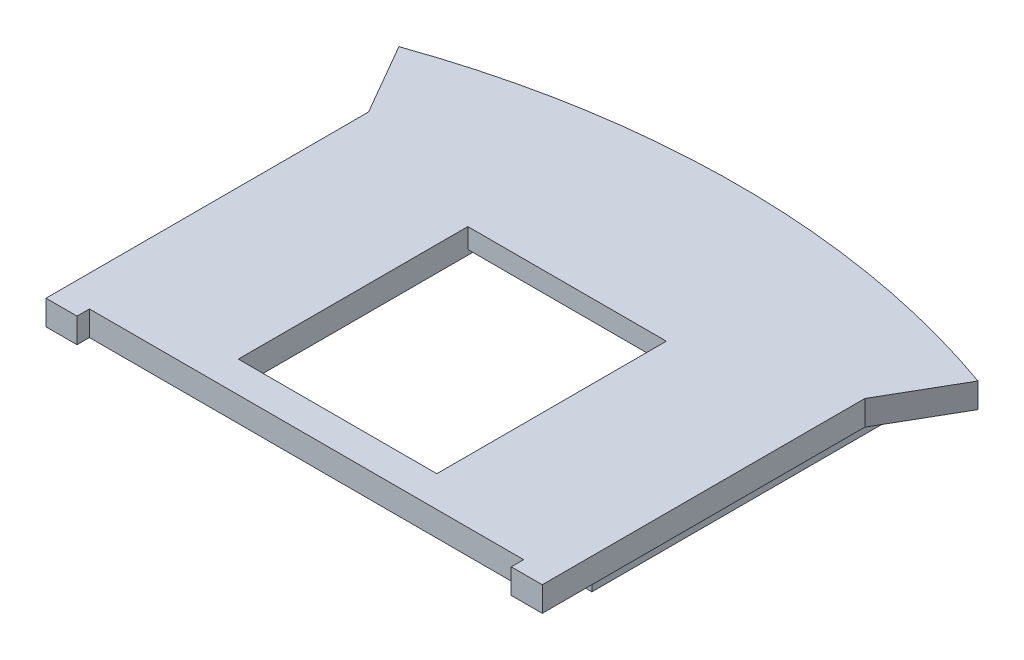
SolidWorks part; units mm, degrees
ref_plane "Front Plane" through (0, 0, 0) normal (0, 0, 1) x (1, 0, 0)
ref_plane "Top Plane" through (0, 0, 0) normal (0, 1, 0) x (1, 0, 0)
ref_plane "Right Plane" through (0, 0, 0) normal (1, 0, 0) x (0, 0, -1)
sketch "Sketch1" plane through (0, 0, 0) normal (0, 1, 0) x (1, 0, 0)
  line L0 (-40, 68) -> (-40, 120)
  line L1 (-40, 120) -> (-46.6772, 131.5652)
  line L2 (46.6772, 131.5652) -> (40, 120)
  line L3 (40, 120) -> (40, 68)
  line L4 (40, 68) -> (-40, 68)
  arc A0 (-46.6772, 131.5652) -> (46.6772, 131.5652) centre (0, 0) cw
  dimension "D1" = 139.6
  dimension "D2" = 150
  dimension "D3" = 40
  dimension "D4" = 80
  dimension "D5" = 150
  dimension "D6" = 52
  dimension "D7" = 68
extrude "Boss-Extrude1" add sketch "Sketch1" along normal blind 4
sketch "Sketch2" plane through (0, 4, 0) normal (0, 1, 0) x (1, 0, 0)
  line L1 (-16, 112) -> (16, 112)
  line L2 (-16, 112) -> (-16, 75)
  line L3 (-16, 75) -> (16, 75)
  line L4 (16, 112) -> (16, 75)
  dimension "D1" = 32
  dimension "D2" = 37
  dimension "D3" = 75
  dimension "D4" = 16
extrude "Cut-Extrude1" cut sketch "Sketch2" against normal up to next
sketch "Sketch3" plane through (0, 0, 0) normal (0, -1, 0) x (1, 0, 0)
  line L0 (16, -75) -> (16, -112) construction
  line L1 (-16, -71.5) -> (16, -71.5)
  line L2 (-16, -71.5) -> (-16, -115.5)
  line L3 (-16, -115.5) -> (16, -115.5)
  line L4 (16, -71.5) -> (16, -115.5)
  line L5 (-16, -112) -> (-16, -75) construction
  line L6 (16, -112) -> (-16, -112) construction
  dimension "D1" = 44
  dimension "D2" = 3.5
extrude "Cut-Extrude2" cut sketch "Sketch3" against normal blind 0.8
sketch "Sketch4" plane through (0, 0, 0) normal (0, -1, 0) x (1, 0, 0)
  line L0 (-38, -78) -> (-38, -128)
  line L1 (-40, -68) -> (40, -68) construction
  line L2 (-38, -128) -> (38, -128)
  line L3 (38, -128) -> (38, -78)
  line L4 (38, -78) -> (35, -78)
  line L5 (35, -78) -> (35, -125)
  line L6 (35, -125) -> (-35, -125)
  line L7 (-35, -125) -> (-35, -78)
  line L8 (-35, -78) -> (-38, -78)
  line L9 (-40, -120) -> (-40, -68) construction
  line L10 (40, -68) -> (40, -120) construction
  dimension "D1" = 2
  dimension "D2" = 3
  dimension "D3" = 2
  dimension "D4" = 3
  dimension "D5" = 57
  dimension "D6" = 10
extrude "Boss-Extrude2" add sketch "Sketch4" along normal blind 3
sketch "Sketch5" plane through (0, 0, 0) normal (0, -1, 0) x (1, 0, 0)
  line L0 (-40, -68) -> (40, -68) construction
  line L1 (-35, -68) -> (35, -68)
  line L2 (-35, -68) -> (-35, -70)
  line L3 (-35, -70) -> (35, -70)
  line L4 (35, -68) -> (35, -70)
  line L5 (-40, -120) -> (-40, -68) construction
  line L6 (40, -68) -> (40, -120) construction
  dimension "D1" = 2
  dimension "D2" = 5
  dimension "D3" = 5
extrude "Cut-Extrude3" cut sketch "Sketch5" against normal up to next
